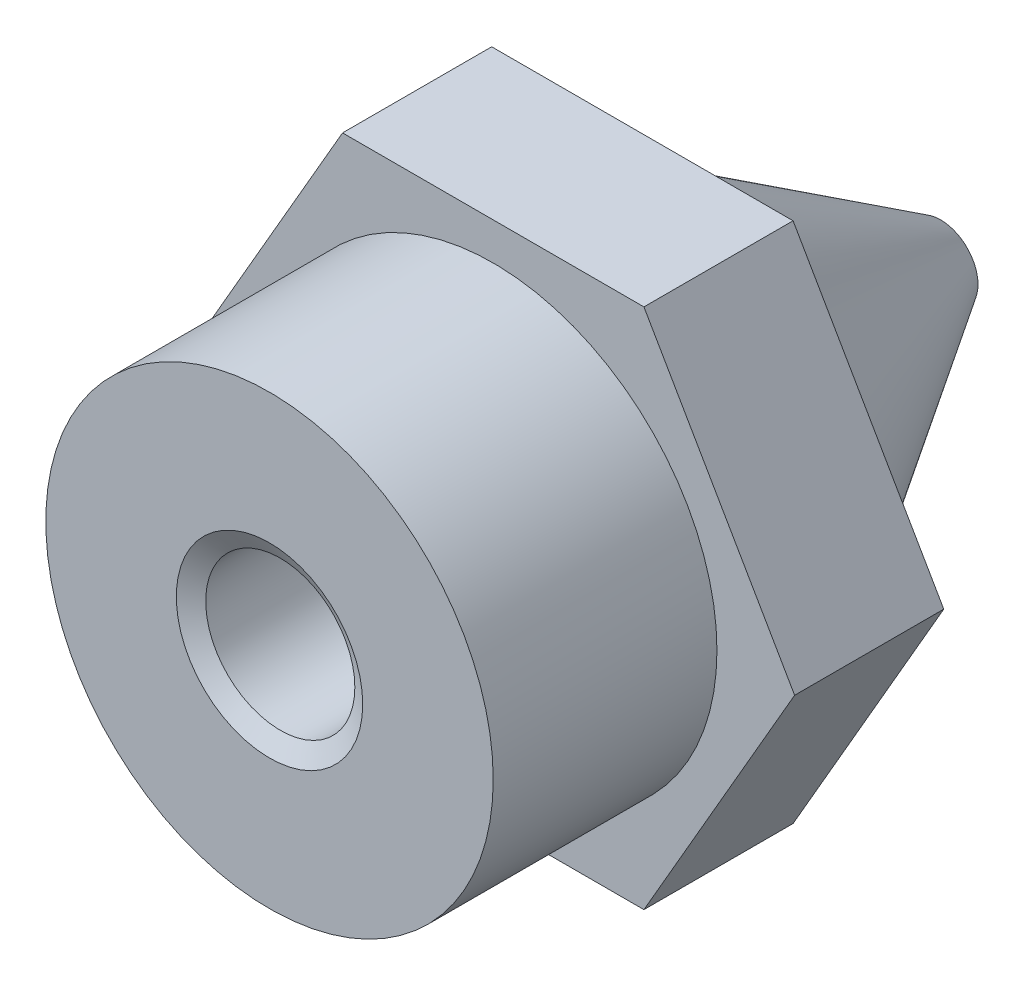
SolidWorks part; units mm, degrees
ref_plane "Plan de face" through (0, 0, 0) normal (0, 0, 1) x (1, 0, 0)
ref_plane "Plan de dessus" through (0, 0, 0) normal (0, 1, 0) x (1, 0, 0)
ref_plane "Plan de droite" through (0, 0, 0) normal (1, 0, 0) x (0, 0, -1)
sketch "Esquisse1" plane through (0, 0, 0) normal (0, 0, 1) x (1, 0, 0)
  line L1 (4.0415, 0) -> (2.0207, 3.5)
  line L2 (2.0207, 3.5) -> (-2.0207, 3.5)
  line L3 (-2.0207, 3.5) -> (-4.0415, 0)
  line L4 (-4.0415, 0) -> (-2.0207, -3.5)
  line L5 (-2.0207, -3.5) -> (2.0207, -3.5)
  line L6 (2.0207, -3.5) -> (4.0415, 0)
  circle A0 centre (0, 0) radius 3.5 construction
  dimension "D1" = 7
extrude "Boss.-Extru.1" add sketch "Esquisse1" along normal blind 9
sketch "Esquisse2" plane through (0, 0, 9) normal (0, 0, 1) x (1, 0, 0)
  line L1 (-7.9912, 5.5023) -> (7.566, 5.5023)
  line L2 (-7.9912, 5.5023) -> (-7.9912, -5.9665)
  line L3 (-7.9912, -5.9665) -> (7.566, -5.9665)
  line L4 (7.566, 5.5023) -> (7.566, -5.9665)
  circle A0 centre (0, 0) radius 3
  dimension "D1" = 6
extrude "Enlèv. mat.-Extru.1" cut sketch "Esquisse2" against normal blind 3
cosmetic thread "Représentation de filetage1" parameters "D2"=4.891
sketch "Esquisse3" plane through (0, 0, 0) normal (0, 0, -1) x (-1, 0, 0)
  line L1 (7.8656, -6.0768) -> (-7.4574, -6.0768)
  line L2 (7.8656, -6.0768) -> (7.8656, 5.7844)
  line L3 (7.8656, 5.7844) -> (-7.4574, 5.7844)
  line L4 (-7.4574, -6.0768) -> (-7.4574, 5.7844)
  circle A0 centre (0, 0) radius 3
  dimension "D1" = 6
extrude "Enlèv. mat.-Extru.3" cut sketch "Esquisse3" against normal blind 4
chamfer "Chanfrein2" distance 4 angle 32 1 edges at (-3, 0, 0) first distance on face at (-3, 0, 4)
sketch "Esquisse4" plane through (0, 0, 0) normal (0, 1, 0) x (1, 0, 0)
  line L0 (0, 0) -> (0, -9) construction
  line L1 (0.5005, 0) -> (-0.5005, 0) construction
  line L2 (-3, -9) -> (3, -9) construction
  line L3 (0, 0) -> (0.2, 0) construction
  line L4 (0, 1.4) -> (1, -6.6) construction
  line L5 (0, 0) -> (0, 1.4) construction
  line L6 (0.2, 0) -> (0.2, -1.4) construction
  line L7 (0.2, -1.4) -> (0, -1.4) construction
  line L8 (0, 1.4) -> (1, -6.6)
  line L9 (1, -6.6) -> (1, -9)
  line L10 (1, -9) -> (0, -9)
  line L11 (0, -9) -> (0, 1.4)
  dimension "D1" = 8
  dimension "D2" = 1
revolve "Enlèvement de matière-Révolution1" cut sketch "Esquisse4" angle 360 about L11
chamfer "Chanfrein3" distance 0.25 angle 30 1 edges at (1, 0, 9) first distance on face at (1, 0, 9)
